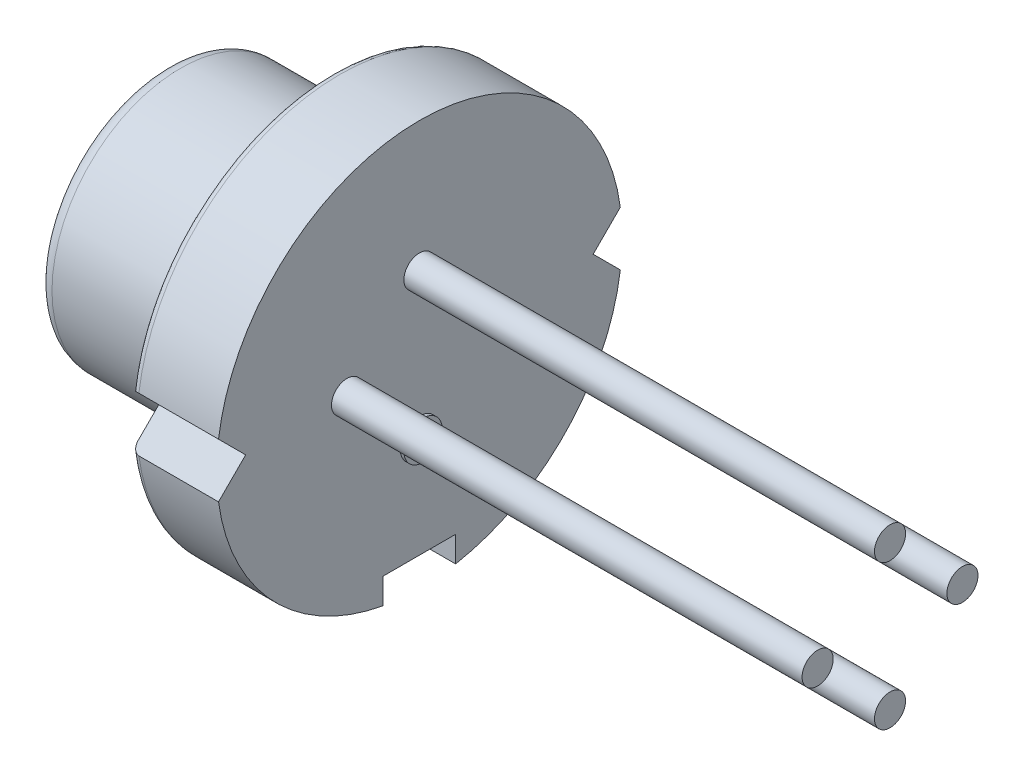
SolidWorks part; units mm, degrees
material "Brass"
ref_plane "Front Plane" through (0, 0, 0) normal (0, 0, 1) x (1, 0, 0)
ref_plane "Top Plane" through (0, 0, 0) normal (0, 1, 0) x (1, 0, 0)
ref_plane "Right Plane" through (0, 0, 0) normal (1, 0, 0) x (0, 0, -1)
sketch "Sketch4" plane through (0, 0, 0) normal (0, 0, 1) x (1, 0, 0)
  line L0 (0, 3.9054) -> (0, -4.2174) construction
  line L1 (-2.4917, 0) -> (5.581, 0) construction
  line L2 (0, 0) -> (0, 0.7)
  line L3 (-1, 0.8) -> (-0.75, 0.8)
  line L4 (2.5, 0) -> (2.5, 2.8)
  line L5 (0, 0) -> (2.5, 0)
  line L6 (-0.75, 0.8) -> (-0.75, 0.7)
  line L7 (-0.75, 0.7) -> (0, 0.7)
  line L8 (2.5, 2.8) -> (1.3, 2.8)
  line L9 (-1, 0.8) -> (-1, 1.775)
  line L11 (-1, 1.775) -> (0.75, 1.775)
  line L13 (1.3, 2.8) -> (1.3, 2.1)
  line L16 (1.3, 2.1) -> (1, 2.1)
  line L18 (1, 2.1) -> (1, 2.025)
  arc A0 (1, 2.025) -> (0.75, 1.775) centre (0.75, 2.025) cw
  dimension "D11" = 0.25
  dimension "D2" = 1.6
  dimension "D3" = 3.55
  dimension "D4" = 4.2
  dimension "D5" = 5.6
  dimension "D6" = 1.3
  dimension "D7" = 0.7
  dimension "D8" = 2.3
  dimension "D9" = 1.2
  dimension "D10" = 0.25
  dimension "D14" = 0.3
revolve "Revolve2" add sketch "Sketch4" angle 360 about L1
sketch "Sketch6" plane through (2.5, 0, 0) normal (1, 0, 0) x (0, 0, -1)
  line L0 (-5.8415, 0) -> (5.3793, 0) construction
  line L1 (0, 5.0519) -> (0, -5.1932) construction
  circle A0 centre (0, 0) radius 1 construction
  circle A1 centre (1, 0) radius 0.215
  circle A2 centre (0, -1) radius 0.215
  circle A3 centre (-1, 0) radius 0.215
  circle A4 centre (0, -1) radius 0.265
  circle A5 centre (0, 1) radius 0.215
  dimension "D1" = 2
  dimension "D2" = 0.43
  dimension "D3" = 0.53
  dimension "D4" = 0.43
extrude "Extrude2" add sketch "Sketch6" along normal blind 6.5 contours A2 | A3 | A1 | A5 region at (2.5, 0, -1) region at (2.5, -1, 0) region at (2.5, 0, 1)
sketch "Sketch8" plane through (2.5, 0, 0) normal (1, 0, 0) x (0, 0, -1)
  line L0 (-4.3892, 0) -> (4.2829, 0) construction
  line L1 (0, 0) -> (0, 4.3747) construction
  line L2 (0, 0) -> (0, -2.8) construction
  line L3 (0, -2.8) -> (0.0051, -4.3895) construction
  line L4 (2.4, 0) -> (2.7748, 0.3748)
  line L5 (0.5, -3.2) -> (-0.5, -3.2)
  line L6 (0.5, -3.2) -> (0.5, -2.4)
  line L7 (0.5, -2.4) -> (-0.5, -2.4)
  line L8 (-0.5, -3.2) -> (-0.5, -2.4)
  line L9 (0.5, -3.2) -> (-0.5, -2.4) construction
  line L10 (0.5, -2.4) -> (-0.5, -3.2) construction
  line L11 (2.4, 0) -> (2.7748, -0.3748)
  line L12 (-2.4, 0) -> (-2.7748, -0.3748)
  line L13 (-2.4, 0) -> (-2.7748, 0.3748)
  circle A0 centre (0, 0) radius 2.8 construction
  point P6 (0, -2.8)
  circle M2 centre (0, 0) radius 2.8
  dimension "D4" = 2.4
  dimension "D1" = 1
  dimension "D2" = 0.8
  dimension "D3" = 90
extrude "Cut-Extrude1" cut sketch "Sketch8" against normal through all contours L12 L13 M2 | L4 L11 M2 | L8 L6 L7 M2 region at (2.5, 0, -2.661) region at (2.5, 0, 2.661) region at (2.5, -2.5928, 0)
sketch "Sketch10" plane through (-0.75, 0, 0) normal (-1, 0, 0) x (0, 0, 1)
  circle A0 centre (0, 0) radius 0.8
fillet "Fillet1" radius 0.2 1 edges at (-1, 0, 1.775)
fillet "Fillet2" radius 0.1 3 edges at (1.3, -1.9346, -2.0242) (1.3, -1.9346, 2.0242) (1.3, 2.8, 0)
extrude "Boss-Extrude2" add sketch "Sketch6<3>" along normal blind 0.05 contours A4 A2 region at (2.5, -1, 0.2575)
sketch "Sketch6<3>" plane through (2.5, 0, 0) normal (1, 0, 0) x (0, 0, -1) same geometry as "Sketch6"
